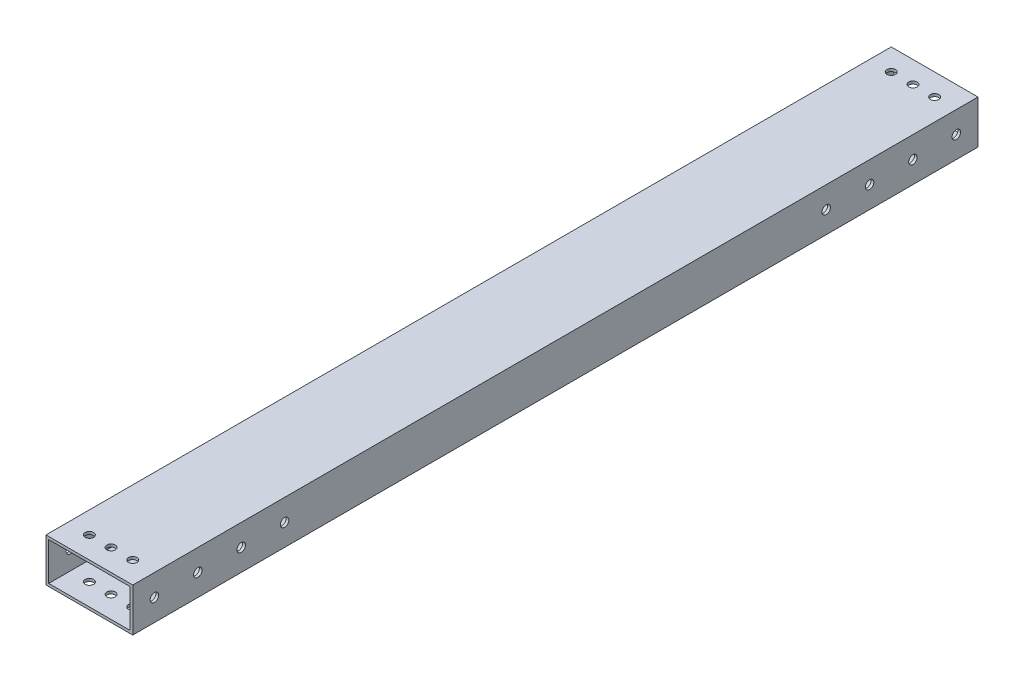
SolidWorks part; units mm, degrees
material "6061-T6 (SS)"
ref_plane "Front Plane" through (0, 0, 0) normal (0, 0, 1) x (1, 0, 0)
ref_plane "Top Plane" through (0, 0, 0) normal (0, 1, 0) x (1, 0, 0)
ref_plane "Right Plane" through (0, 0, 0) normal (1, 0, 0) x (0, 0, -1)
sketch "Sketch1" plane through (0, 0, 0) normal (0, 0, 1) x (1, 0, 0)
  line L0 (-23.8125, 11.1125) -> (23.8125, 11.1125)
  line L1 (-25.4, -12.7) -> (25.4, -12.7)
  line L2 (-25.4, -12.7) -> (-25.4, 12.7)
  line L3 (-25.4, 12.7) -> (25.4, 12.7)
  line L4 (25.4, -12.7) -> (25.4, 12.7)
  line L5 (-25.4, -12.7) -> (25.4, 12.7) construction
  line L6 (-25.4, 12.7) -> (25.4, -12.7) construction
  line L7 (23.8125, -11.1125) -> (23.8125, 11.1125)
  line L8 (-23.8125, -11.1125) -> (23.8125, -11.1125)
  line L9 (-23.8125, -11.1125) -> (-23.8125, 11.1125)
  point P0 (0, 0)
  dimension "D1" = 50.8
  dimension "D2" = 25.4
  dimension "D3" = 1.5875
extrude "Boss-Extrude1" add sketch "Sketch1" along normal mid plane 494.919
sketch "Sketch2" plane through (0, 12.7, 0) normal (0, 1, 0) x (1, 0, 0)
  line L0 (25.4, 247.4595) -> (-25.4, 247.4595) construction
  line L1 (-25.4, 0) -> (25.4, 0) construction
  line L2 (-25.4, -247.4595) -> (-25.4, 247.4595) construction
  line L3 (25.4, -247.4595) -> (25.4, 247.4595) construction
  circle A0 centre (-12.7, 234.7595) radius 2.4892
  circle A1 centre (0, 234.7595) radius 2.4892
  circle A2 centre (12.7, 234.7595) radius 2.4892
  circle A3 centre (12.7, -234.7595) radius 2.4892
  circle A4 centre (0, -234.7595) radius 2.4892
  circle A5 centre (-12.7, -234.7595) radius 2.4892
  point P9 (0, 247.4595)
  dimension "D1" = 4.9784
  dimension "D2" = 12.7
  dimension "D3" = 12.7
  dimension "D4" = 12.7
extrude "Cut-Extrude1" cut sketch "Sketch2" against normal through all
sketch "Sketch3" plane through (25.4, 0, 0) normal (1, 0, 0) x (0, 0, -1)
  line L0 (247.4595, -12.7) -> (247.4595, 12.7) construction
  line L1 (0, 12.7) -> (0, -12.7) construction
  line L2 (-247.4595, 12.7) -> (247.4595, 12.7) construction
  line L3 (-247.4595, -12.7) -> (247.4595, -12.7) construction
  circle A0 centre (234.7595, 0) radius 2.4892
  circle A1 centre (-234.7595, 0) radius 2.4892
  circle A2 centre (209.3595, 0) radius 2.4892
  circle A3 centre (183.9595, 0) radius 2.4892
  circle A4 centre (158.5595, 0) radius 2.4892
  circle A7 centre (-158.5595, 0) radius 2.4892
  circle A8 centre (-183.9595, 0) radius 2.4892
  circle A9 centre (-209.3595, 0) radius 2.4892
  point P5 (247.4595, 0)
  dimension "D1" = 12.7
  dimension "D2" = 4.9784
  dimension "D4" = 25.4
  dimension "D3" = 4
extrude "Cut-Extrude2" cut sketch "Sketch3" against normal through all
